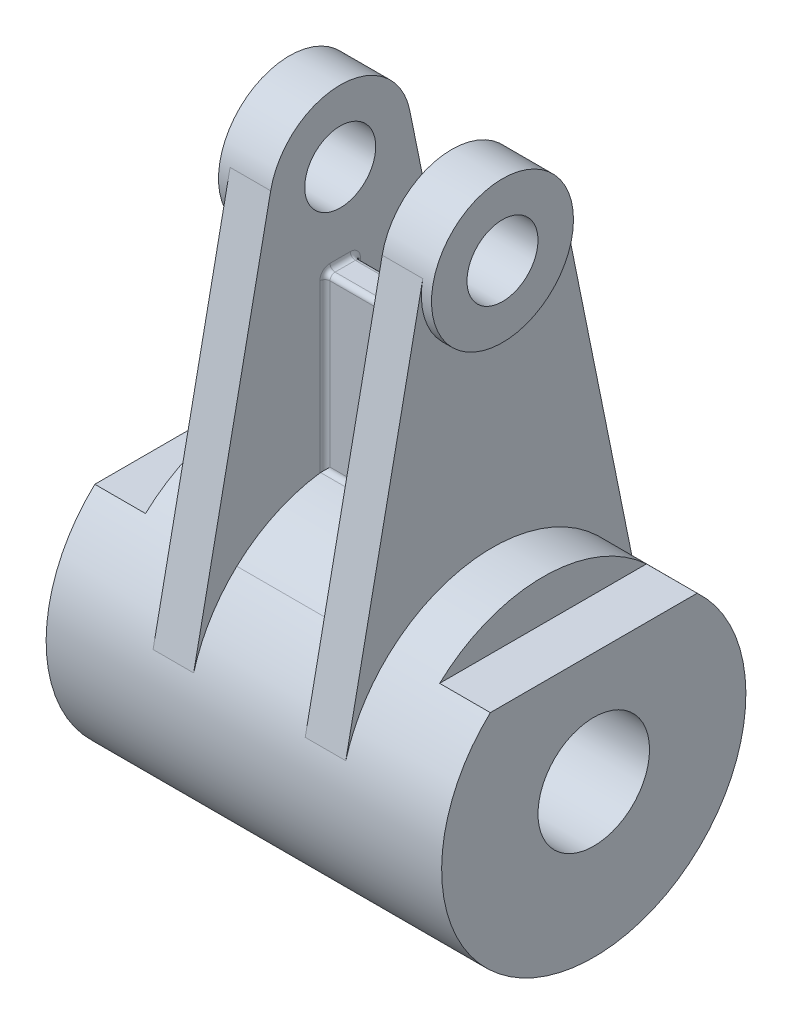
SolidWorks part; units mm, degrees
ref_plane "Front Plane" through (0, 0, 0) normal (0, 0, 1) x (1, 0, 0)
ref_plane "Top Plane" through (0, 0, 0) normal (0, 1, 0) x (1, 0, 0)
ref_plane "Right Plane" through (0, 0, 0) normal (1, 0, 0) x (0, 0, -1)
sketch "Sketch1" plane through (0, 0, 0) normal (1, 0, 0) x (0, 0, -1)
  circle A0 centre (0, 0) radius 30
  circle A1 centre (0, 0) radius 11
  dimension "D1" = 60
  dimension "D2" = 22
extrude "Boss-Extrude1" add sketch "Sketch1" along normal mid plane 78
sketch "Sketch2" plane through (0, 0, 0) normal (1, 0, 0) x (0, 0, -1)
  circle A0 centre (0, 0) radius 18
  dimension "D1" = 36
extrude "Cut-Extrude1" cut sketch "Sketch2" against normal mid plane 36 contours A0
sketch "Sketch3" plane through (0, 0, 0) normal (0, 1, 0) x (1, 0, 0)
  circle A0 centre (0, 0) radius 8
  dimension "D1" = 16
extrude "Cut-Extrude2" cut sketch "Sketch3" against normal blind 36
sketch "Sketch4" plane through (39, 0, 0) normal (1, 0, 0) x (0, 0, -1)
  line L0 (-20.3961, 22) -> (20.3961, 22)
  circle A0 centre (0, 0) radius 30 construction
  arc A1 (20.3961, 22) -> (-20.3961, 22) centre (0, 0) ccw
  point P4 (0, -30)
  dimension "D1" = 52
extrude "Cut-Extrude3" cut sketch "Sketch4" against normal blind 10
mirror "Mirror1" about plane through (0, 0, 0) normal (1, 0, 0) of "Cut-Extrude3"
sketch "Sketch5" plane through (29, 0, 0) normal (1, 0, 0) x (0, 0, -1)
  line L0 (0, 0) -> (0, 80) construction
  line L1 (-13.7198, 82.7869) -> (-29.7477, 3.8824)
  line L2 (13.7198, 82.7869) -> (29.7477, 3.8824)
  circle A0 centre (0, 80) radius 7
  circle A1 centre (0, 80) radius 14
  arc A2 (-20.3961, 22) -> (20.3961, 22) centre (0, 0) ccw construction
  arc A3 (29.7477, 3.8824) -> (-29.7477, 3.8824) centre (0, 0) ccw
  dimension "D2" = 14
  dimension "D3" = 28
  dimension "D1" = 80
  dimension "D4" = 6.6763
extrude "Boss-Extrude2" add sketch "Sketch5" along normal blind 10 from offset 18 separate body contours A1 A0 region at (29, 93.604, 0) offset against normal yes
extrude "Boss-Extrude3" add sketch "Sketch5<3>" along normal blind 8 from offset 18 contours A3 L0 A1 L1 | L0 L2 A3 A1 region at (29, 45.7984, 11.8488) region at (29, 45.7984, -11.8488) offset against normal yes
sketch "Sketch5<3>" plane through (29, 0, 0) normal (1, 0, 0) x (0, 0, -1) same geometry as "Sketch5"
mirror "Mirror6" about plane through (0, 0, 0) normal (1, 0, 0) of "Boss-Extrude3"
sketch "Sketch6" plane through (-11, 0, 0) normal (1, 0, 0) x (0, 0, -1)
  circle A0 centre (0, 80) radius 7 construction
  circle A1 centre (0, 80) radius 14 construction
  circle A2 centre (0, 80) radius 7
  circle A3 centre (0, 80) radius 14
extrude "Boss-Extrude4" add sketch "Sketch6" against normal blind 10
sketch "Sketch7" plane through (11, 0, 0) normal (-1, 0, 0) x (0, 0, 1)
  line L2 (-2.9854, 29.8511) -> (-2.9854, 63.5482)
  line L3 (-2.9854, 63.5482) -> (3.0146, 63.5482)
  line L4 (3.0146, 29.8482) -> (3.0146, 63.5482)
  arc A2 (20.3961, 22) -> (-20.3961, 22) centre (0, 0) ccw construction
  arc A3 (3.0146, 29.8482) -> (-2.9854, 29.8511) centre (0, 0) ccw
  point P0 (0, 46.85)
  point P10 (0, 0)
  point P11 (0, 0)
  point P12 (0, 0)
  dimension "D1" = 10.7344
  dimension "D2" = 6
  dimension "D3" = 13.7198
  dimension "D4" = 19.2388
  dimension "D5" = 35.9369
extrude "Boss-Extrude7" add sketch "Sketch7" along normal up to next
fillet "Fillet1" radius 1 10 edges at (11, 63.5482, 0.0146) (-11, 63.5482, 0.0146) (0, 63.5482, 3.0146) (11, 46.6982, 3.0146) (0, 29.8482, 3.0146) (-11, 46.6982, 3.0146) (0, 29.8511, -2.9854) (11, 46.6996, -2.9854) (0, 63.5482, -2.9854) (-11, 46.6996, -2.9854)
sketch "Sketch10" plane through (0, 0, -2.9854) normal (0, 0, -1) x (-1, 0, 0)
  line L0 (29, 30) -> (19, 30) construction
  circle A0 centre (0, 48) radius 3
  dimension "D1" = 6
  dimension "D2" = 18
extrude "Cut-Extrude4" cut sketch "Sketch10" against normal blind 18
thread "Thread2" pitch 1.5 method cut profile "Thread Profile3" start angle 0, offset 0, length 20, pitch 1.5, diameter 6
ref_plane "Plane3" through (3, 48, -2.9854) normal (0, -1, 0) x (1, 0, 0)
sketch "Thread Profile3" plane through (3, 48, -2.9854) normal (0, -1, 0) x (1, 0, 0)
  line L0 (0, 0) -> (0, 1.5) construction
  line L1 (0, 0) -> (0.8119, 0.4687)
  line L2 (0.8119, 0.4687) -> (0.8119, 0.6562)
  line L3 (0.8119, 0.6562) -> (0, 1.125)
  line L4 (0.8119, 0.5625) -> (0, 0.5625) construction
  line L11 (0, 0) -> (0, 1.125)
  point P2 (0, 0)
  dimension "Pitch" = 1.5
  dimension "Profile_Angle" = 60
  dimension "Profile_Land" = 0.1875
  dimension "Profile_Height" = 0.8119
